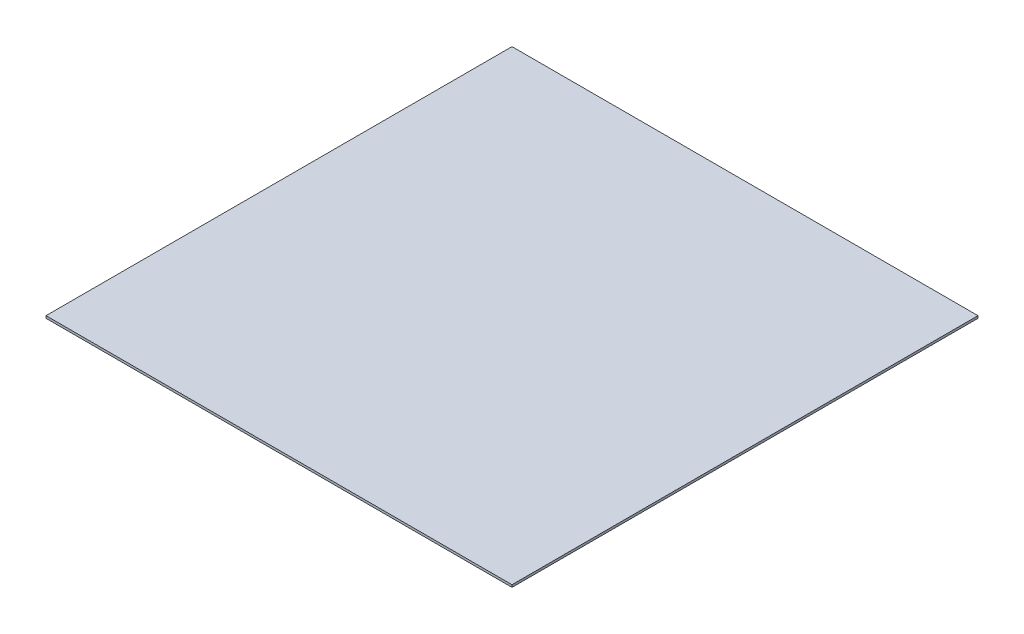
SolidWorks part; units mm, degrees
material "Plain Carbon Steel"
ref_plane "FRONT" through (0, 0, 0) normal (0, 0, 1) x (1, 0, 0)
ref_plane "TOP" through (0, 0, 0) normal (0, 1, 0) x (1, 0, 0)
ref_plane "RIGHT" through (0, 0, 0) normal (1, 0, 0) x (0, 0, -1)
ref_axis "Axis1" through (-80.9, 0, 0) along (1, 0, 0)
ref_axis "Axis2" through (0, 0, -80.9) along (0, 0, 1)
ref_axis "Axis3" through (0, 50, 0) along (0, -1, 0)
sketch "Sketch1" plane through (0, 0, 0) normal (0, 1, 0) x (1, 0, 0)
  line L1 (-100, -100) -> (100, -100)
  line L2 (-100, -100) -> (-100, 100)
  line L3 (-100, 100) -> (100, 100)
  line L4 (100, -100) -> (100, 100)
  line L5 (-100, -100) -> (100, 100) construction
  line L6 (-100, 100) -> (100, -100) construction
  point P0 (0, 0)
  dimension "D1" = 200
  dimension "D2" = 200
extrude "Boss-Extrude1" add sketch "Sketch1" along normal blind 1
equation "\"D1@Sketch1\"=\"D2@Sketch1\""
